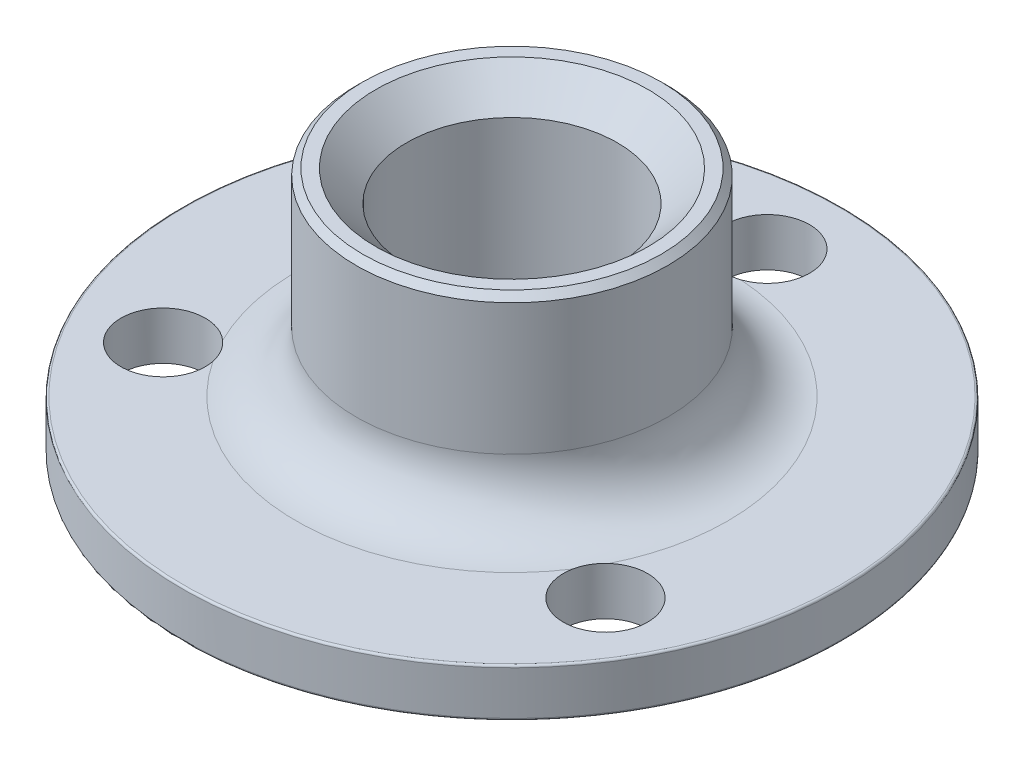
SolidWorks part; units mm, degrees
ref_plane "Front Plane" through (0, 0, 0) normal (0, 0, 1) x (1, 0, 0)
ref_plane "Top Plane" through (0, 0, 0) normal (0, 1, 0) x (1, 0, 0)
ref_plane "Right Plane" through (0, 0, 0) normal (1, 0, 0) x (0, 0, -1)
sketch "Sketch1" plane through (0, 0, 0) normal (0, 1, 0) x (1, 0, 0)
  line L0 (0, -6.35) -> (0, 0) construction
  line L1 (0, 0) -> (3.175, -5.4993) construction
  circle A0 centre (0, 0) radius 15.875 construction
  circle A1 centre (0, 0) radius 7.5057 construction
  circle A2 centre (0, 12.3031) radius 2.032 construction
  circle A3 centre (0, 0) radius 12.3031 construction
  circle A4 centre (10.6548, -6.1516) radius 2.032 construction
  circle A5 centre (-10.6548, -6.1516) radius 2.032 construction
  circle A6 centre (0, 0) radius 6.35 construction
  point P8 (3.175, -5.4993)
  point P13 (0, 0)
  dimension "Base Diameter" = 31.75
  dimension "Barrel Diameter" = 15.0114
  dimension "Mounting Hole Diameter" = 4.064
  dimension "Bolt Hole Circle" = 24.6062
  dimension "Thread Size" = 12.7
  dimension "D1" = 30
  dimension "Number of Mounting Holes" = 3
sketch "Sketch2" plane through (0, 0, 0) normal (0, 0, 1) x (1, 0, 0)
  line L0 (-15.875, -5.9182) -> (-15.875, -3.6068) construction
  line L1 (-6.35, 5.9182) -> (-6.35, -5.9182) construction
  line L3 (-7.5057, -5.9182) -> (-7.5057, -3.6068) construction
  line L4 (15.875, 0) -> (-15.875, 0) construction
  line L5 (6.35, 0) -> (-6.35, 0) construction
  line L6 (7.5057, 0) -> (-7.5057, 0) construction
  line L7 (-7.5057, -3.6068) -> (-7.5057, 5.9182) construction
  line L8 (-6.5615, 5.7961) -> (-6.5615, 7.7499) construction
  line L9 (-6.5615, 7.7499) -> (-4.8694, 6.773) construction
  line L10 (-4.8694, 6.773) -> (-6.5615, 5.7961) construction
  line L11 (-6.35, 5.9182) -> (-6.35, 7.6278) construction
  line L12 (-5.0809, 6.6509) -> (-5.0809, 6.8951) construction
  line L13 (-5.0809, 6.773) -> (-4.8694, 6.773) construction
  line L14 (-6.35, 6.773) -> (-6.5615, 6.773) construction
  line L15 (15.875, 0) -> (-15.875, 0) construction
  line L16 (6.35, 0) -> (-6.35, 0) construction
  line L17 (-5.0809, 6.6509) -> (-5.0809, 6.8951) construction
  line L18 (-5.0809, 6.8951) -> (-6.4558, 7.6889) construction
  line L19 (-6.4558, 7.6889) -> (-6.4558, 5.8571) construction
  line L20 (-6.4558, 5.8571) -> (-5.0809, 6.6509) construction
  line L21 (0, -5.9182) -> (0, 5.9182) construction
  line L22 (7.5057, 0) -> (-7.5057, 0) construction
  point P19 (-6.4558, 6.773)
  point P25 (0, 0)
  dimension "Base Thickness" = 2.3114
  dimension "Barrel Height" = 9.525
  dimension "Thread Pitch" = 1.9538
  dimension "Pitch/8" = 0.2442
sketch "Sketch3" plane through (0, 0, 0) normal (0, 0, 1) x (1, 0, 0)
  line L0 (-5.0809, -3.0289) -> (-5.0809, 4.4376)
  line L1 (-6.5615, 5.9182) -> (-7.5057, 5.9182)
  line L3 (-7.5057, -3.6068) -> (-7.5057, 5.9182) construction
  line L4 (-7.5057, 5.9182) -> (-7.5057, -0.7175)
  line L5 (-10.3949, -3.6068) -> (-15.875, -3.6068)
  line L6 (-15.875, -3.6068) -> (-15.875, -5.9182)
  line L8 (-6.5615, 5.7961) -> (-6.5615, 7.7499) construction
  line L9 (-15.875, -5.9182) -> (-7.9702, -5.9182)
  line L10 (-6.5615, 5.9182) -> (-5.0809, 4.4376)
  line L11 (0, 0) -> (0, 9.525) construction
  line L14 (-5.0809, 6.6509) -> (-5.0809, 6.8951) construction
  arc A0 (-7.5057, -0.7175) -> (-10.3949, -3.6068) centre (-10.3949, -0.7175) cw
  arc A2 (-7.9702, -5.9182) -> (-5.0809, -3.0289) centre (-7.9702, -3.0289) ccw
  dimension "D3" = 2.8892
  dimension "D1" = 45
  dimension "D4" = 0.9442
revolve "Revolve1" add sketch "Sketch3" angle 360 about L21
sketch "Sketch4" plane through (0, 0, 0) normal (0, 1, 0) x (1, 0, 0)
  circle A0 centre (0, 12.3031) radius 2.032
  circle A1 centre (0, 12.3031) radius 2.032 construction
  circle A2 centre (10.6548, -6.1516) radius 2.032
  circle A3 centre (-10.6548, -6.1516) radius 2.032
  point P10 (0, 0)
extrude "Cut-Extrude1" cut sketch "Sketch4" along normal through all both and the other way through all
fillet "Fillet1" radius 0.0992 2 edges at (15.875, -3.6068, 0) (15.875, -5.9182, 0)
chamfer "Chamfer1" distance 0.3147 angle 45 1 edges at (7.5057, 5.9182, 0)
sketch "Sketch9" [suppressed] plane through (0, 5.9182, 0) normal (0, 1, 0) x (1, 0, 0)
  circle A1 centre (0, 0) radius 6.35
  circle A2 centre (0, 0) radius 6.35 construction
extrude "Boss-Extrude1" [suppressed] add sketch "Sketch9" against normal offset from surface (13.7902 mm away) 1.9538 separate body offset beyond the face yes
sketch "Sketch10" [suppressed] plane through (0, 5.9182, 0) normal (0, 1, 0) x (1, 0, 0)
  circle A1 centre (0, 0) radius 6.35
  circle A2 centre (0, 0) radius 6.35
  dimension "D1" = 0
curve "Helix/Spiral2" [suppressed] pitch 1.9538 height 15.7441 turns 8.058
sketch "Sketch11" [suppressed] plane through (0, 0, 0) normal (0, 0, 1) x (1, 0, 0)
  line L0 (-5.0809, 6.6509) -> (-5.0809, 6.8951) construction
  line L1 (-6.4558, 7.6889) -> (-6.4558, 5.8571) construction
  line L2 (-5.0809, 6.6509) -> (-5.0809, 6.8951)
  line L3 (-6.4558, 7.6889) -> (-6.4558, 5.8571)
  line L4 (-6.4558, 5.8571) -> (-5.0809, 6.6509)
  line L5 (-5.0809, 6.8951) -> (-6.4558, 7.6889)
sweep "Cut-Sweep1" [suppressed] cut profiles "Sketch11" path "Helix/Spiral2"
combine bodies "Combine1" [suppressed] operation type subtract main body 105 bodies to subtract 123
equation "\"Pitch/8@Sketch2\" = \"Thread Pitch@Sketch2\" / 8"
equation "\"D1@Sketch4\"=\"Number of Mounting Holes@Sketch1\""
equation "\"D3@Sketch3\"=\"Base Thickness@Sketch2\" * 1.25"
equation "\"D1@Chamfer1\"=\"D4@Sketch3\" / 3"
equation "\"D1@Boss-Extrude1\"=\"Thread Pitch@Sketch2\""
equation "\"D4@Helix/Spiral2\"=\"Thread Pitch@Sketch2\""
equation "\"D3@Helix/Spiral2\"=\"Barrel Height@Sketch2\" + \"Base Thickness@Sketch2\" + 2 * \"Thread Pitch@Sketch2\""
